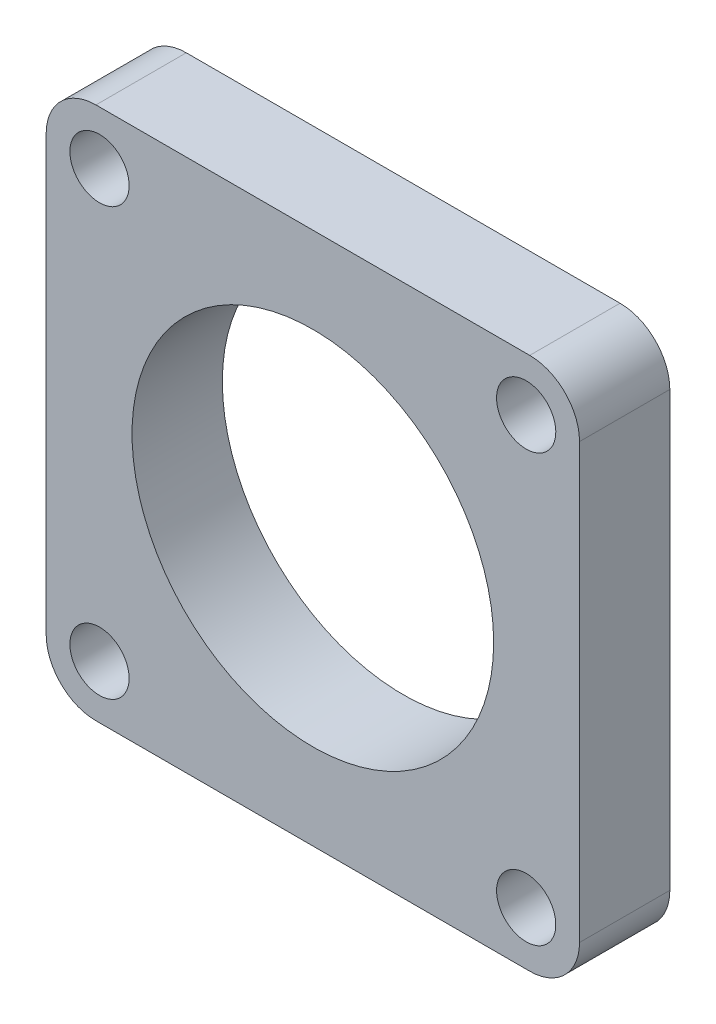
SolidWorks part; units mm, degrees
ref_plane "Front" through (0, 0, 0) normal (0, 0, 1) x (1, 0, 0)
ref_plane "Top" through (0, 0, 0) normal (0, 1, 0) x (1, 0, 0)
ref_plane "Right" through (0, 0, 0) normal (1, 0, 0) x (0, 0, -1)
sketch "Sketch1" plane through (0, 0, 0) normal (0, 0, 1) x (1, 0, 0)
  line L1 (-37.5, -37.5) -> (37.5, -37.5)
  line L2 (-37.5, -37.5) -> (-37.5, 37.5)
  line L3 (-37.5, 37.5) -> (37.5, 37.5)
  line L4 (37.5, -37.5) -> (37.5, 37.5)
  line L5 (-37.5, -37.5) -> (37.5, 37.5) construction
  line L6 (-37.5, 37.5) -> (37.5, -37.5) construction
  point P0 (0, 0)
  dimension "D1" = 75
  dimension "D2" = 75
extrude "Boss-Extrude1" add sketch "Sketch1" along normal blind 12.7
fillet "Fillet1" radius 7 4 edges at (-37.5, -37.5, 6.35) (37.5, -37.5, 6.35) (-37.5, 37.5, 6.35) (37.5, 37.5, 6.35)
sketch "Sketch2" plane through (0, 0, 12.7) normal (0, 0, 1) x (1, 0, 0)
  circle A0 centre (0, 0) radius 25.4254
  dimension "D1" = 50.8508
extrude "Cut-Extrude1" cut sketch "Sketch2" against normal up to next
sketch "Sketch3" plane through (0, 0, 12.7) normal (0, 0, 1) x (1, 0, 0)
  line L0 (30.5, 37.5) -> (-30.5, 37.5) construction
  line L1 (-37.5, 30.5) -> (-37.5, -30.5) construction
  circle A0 centre (-30, 30) radius 4.165
  dimension "D1" = 8.33
  dimension "D2" = 7.5
  dimension "D3" = 7.5
extrude "Cut-Extrude2" cut sketch "Sketch3" against normal up to next
pattern_circular "CirPattern1" count 4 over 360 about axis through (0, 0, -0.001) along (0, 0, 1) of "Cut-Extrude2" reverse direction yes
